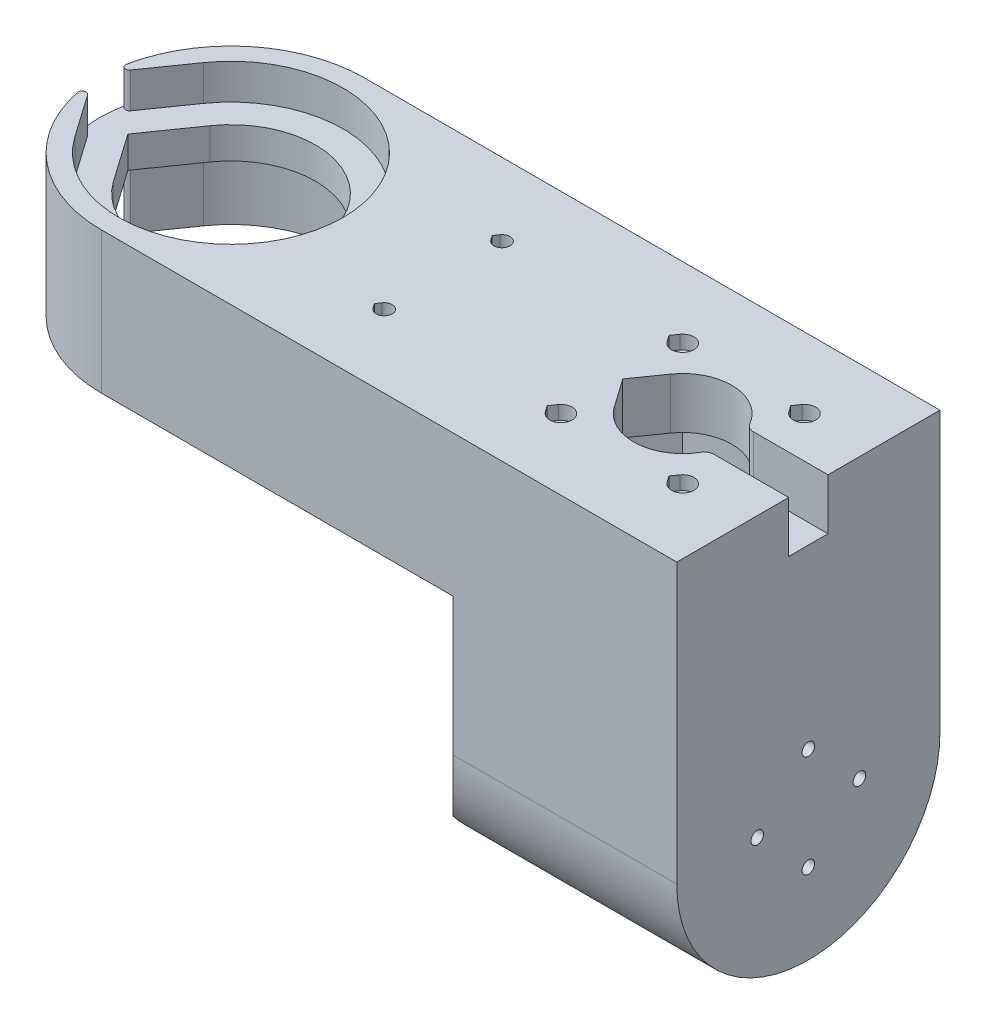
SolidWorks part; units mm, degrees
ref_plane "Front Plane" through (0, 0, 0) normal (1, 0, 0) x (0, 1, 0)
ref_plane "Top Plane" through (0, 0, 0) normal (0, 0, 1) x (0, 1, 0)
ref_plane "Right Plane" through (0, 0, 0) normal (0, 1, 0) x (-1, 0, 0)
sketch "Sketch1" plane through (0, 0, 0) normal (0, 0, 1) x (0, 1, 0)
  line L0 (45, 28.55) -> (54, 28.55)
  line L1 (-7, -93) -> (58, -93)
  line L2 (-7, -93) -> (-7, -137)
  line L3 (-7, -137) -> (58, -137)
  line L4 (58, -93) -> (58, -137)
  line L5 (59, 28.55) -> (68, 28.55)
  line L6 (59, 28.55) -> (59, -28.55)
  line L7 (59, -28.55) -> (68, -28.55)
  line L8 (68, 28.55) -> (68, -28.55)
  line L9 (45, 28.55) -> (45, -28.55)
  line L10 (45, -28.55) -> (54, -28.55)
  line L11 (54, 28.55) -> (54, -28.55)
  line L12 (-13, -147) -> (13, -147)
  line L13 (-30, 30.9464) -> (30, 30.9464) construction
  line L14 (-30, 30.9464) -> (-30, -30.2553) construction
  line L15 (-30, -30.2553) -> (30, -30.2553) construction
  line L16 (30, 30.9464) -> (30, -30.2553) construction
  line L17 (-25, -83) -> (81, -83)
  line L20 (81, -83) -> (81, -147)
  line L21 (81, -83) -> (35, -83)
  line L23 (81, 33.5) -> (35, 33.5)
  line L25 (-25, -147) -> (-13, -147)
  line L26 (-25, -147) -> (-25, -150)
  line L27 (-25, -150) -> (25, -150)
  line L28 (25, -147) -> (25, -150)
  line L29 (13, -147) -> (25, -147)
  line L30 (25, -147) -> (81, -147)
  line L31 (81, -83) -> (81, 33.5)
  line L32 (35, 33.5) -> (35, -83)
  line L33 (-25, -147) -> (-33.5, -147)
  line L34 (-25, -83) -> (-33.5, -83)
  line L35 (-33.5, -83) -> (-33.5, -147)
  point P8 (0, -30.2553)
  point P14 (68, 0)
  point P15 (58, -115)
  point P24 (45, 0)
  point P35 (0, -147)
  dimension "D1" = 65
  dimension "D2" = 44
  dimension "D3" = 57.1
  dimension "D4" = 9
  dimension "D5" = 57.1
  dimension "D6" = 9
  dimension "D7" = 115
  dimension "D8" = 60
  dimension "D9" = 5
  dimension "D10" = 15
  dimension "D11" = 10
  dimension "D12" = 3
  dimension "D13" = 50
  dimension "D14" = 26
  dimension "D15" = 10
  dimension "D16" = 23
  dimension "D17" = 4.95
  dimension "D18" = 10
  dimension "D19" = 10
  dimension "D20" = 8.5
extrude "Boss-Extrude1" add sketch "Sketch1" along normal blind 67 contours L29 L30 L20 L17 L25 L12 L1 L4 L3 L2 | L4 L1 L2 L3 | L23 L32 L17 L31 L0 L11 L10 L9 L5 L8 L7 L6 | L11 L0 L9 L10 | L8 L5 L6 L7 region at (0, 49.5, 0) region at (115, 25.5, 0) region at (0, 63.5, 0) region at (145.6883, -19, 0) region at (30.6232, 58.356, 0)
sketch "Sketch2" plane through (0, 81, 0) normal (0, 1, 0) x (-1, 0, 0)
  line L0 (-56.7259, 33.5) -> (49943.2741, 33.5) construction
  line L1 (-147, 67) -> (-147, 0) construction
  line L2 (17.6118, 21.1681) -> (26.2467, 33.5)
  line L3 (-115, -14.8158) -> (-54, -14.8158) construction
  line L4 (-93, 0) -> (-137, 0) construction
  line L5 (-93, 0) -> (-137, 0) construction
  line L9 (-147, 16) -> (-147, 51)
  line L10 (33.5473, 15.9815) -> (-147, 51) construction
  line L11 (33.5482, 51) -> (-147, 16) construction
  line L12 (-54, 18.5) -> (-54, 48.5) construction
  line L13 (-104.0826, 51) -> (-125.9174, 51)
  line L14 (-130.5, 49) -> (-99.5, 49) construction
  line L15 (-130.5, 49) -> (-130.5, 18) construction
  line L16 (-130.5, 18) -> (-99.5, 18) construction
  line L17 (-99.5, 49) -> (-99.5, 18) construction
  line L18 (-130.5, 49) -> (-99.5, 18) construction
  line L19 (-130.5, 18) -> (-99.5, 49) construction
  line L20 (-135.0826, 51) -> (-147, 51)
  line L21 (-135.0826, 16) -> (-147, 16)
  line L22 (-104.0826, 16) -> (-125.9174, 16)
  line L27 (33.5, 67) -> (-21.8575, 67)
  line L28 (33.5, 0) -> (33.5, 67)
  line L29 (33.5, 67) -> (-147, 67) construction
  line L30 (33.5, 0) -> (-21.8575, 0)
  line L31 (28.55, 0) -> (-28.55, 0) construction
  line L34 (23.3868, 17.1244) -> (34.8531, 33.5)
  line L35 (34.8531, 33.5) -> (23.3868, 49.8756)
  line L36 (26.2467, 33.5) -> (17.6118, 45.8319)
  line L37 (-94.9174, 16) -> (-66.0711, 16)
  line L38 (-94.9174, 51) -> (-66.0711, 51)
  line L39 (-61.0711, 11) -> (-61.0711, 0)
  line L40 (33.5, 0) -> (-147, 0) construction
  line L41 (-61.0711, 56) -> (-61.0711, 67)
  line L42 (33.5, 67) -> (-147, 67) construction
  line L43 (-61.0711, 0) -> (-21.8575, 0)
  line L44 (-61.0711, 67) -> (-21.8575, 67)
  arc A0 (23.3868, 49.8756) -> (23.3868, 17.1244) centre (0, 33.5) ccw
  arc A2 (-39.8663, 36.7683) -> (-39.8653, 30.2204) centre (0, 33.5) ccw
  arc A5 (-135.0826, 16) -> (-125.9174, 16) centre (-130.5, 18) ccw
  arc A6 (-104.0826, 16) -> (-94.9174, 16) centre (-99.5, 18) ccw
  arc A9 (-125.9174, 51) -> (-135.0826, 51) centre (-130.5, 49) ccw
  arc A11 (-94.9174, 51) -> (-104.0826, 51) centre (-99.5, 49) ccw
  arc A12 (17.6118, 45.8319) -> (17.6118, 21.1681) centre (0, 33.5) ccw
  arc A13 (17.6118, 45.8319) -> (17.6118, 21.1681) centre (0, 33.5) cw construction
  arc A15 (23.3868, 17.1244) -> (23.3868, 49.8756) centre (0, 33.5) ccw construction
  arc A16 (-66.0711, 16) -> (-61.0711, 11) centre (-66.0711, 11) cw
  arc A17 (-66.0711, 51) -> (-61.0711, 56) centre (-66.0711, 56) ccw
  point P4 (-56.7259, 33.5)
  point P9 (-56.75, 33.4953)
  point P23 (-115, 33.5)
  point P39 (33.5, 33.5)
  point P61 (-54, 33.5)
  dimension "D1" = 57.1
  dimension "D2" = 35
  dimension "D3" = 80
  dimension "D6" = 5
  dimension "D9" = 10
  dimension "D10" = 43
  dimension "D11" = 55
  dimension "D12" = 10
  dimension "D4" = 61
  dimension "D5" = 30
  dimension "D8" = 31
  dimension "D13" = 55
extrude "Cut-Extrude1" cut sketch "Sketch2" against normal through all both and the other way through all contours A12 L2 L36
fillet "Fillet3" radius 34 2 edges at (-33.5, 58, 0) (-33.5, 58, 67)
extrude "Cut-Extrude2" cut sketch "Sketch2<4>" against normal blind 10 and the other way through all contours L20 L9 L21 A5 L22 A6 L37 A16 L39 L43 L30 L28 L27 L44 L41 A17 L38 A11 L13 A9
sketch "Sketch2<4>" plane through (0, 81, 0) normal (0, 1, 0) x (-1, 0, 0) same geometry as "Sketch2"
extrude "Cut-Extrude3" cut sketch "Sketch2<5>" against normal blind 9 from surface contours A0 L34 L35 starting at face at (81.1646, 71, 33.5)
sketch "Sketch2<5>" plane through (0, 81, 0) normal (0, 1, 0) x (-1, 0, 0) same geometry as "Sketch2"
extrude "Cut-Extrude4" cut sketch "Sketch2<6>" along normal blind 19 from surface contours A0 L34 L35 starting at face at (-7.4528, 35, 33.5)
sketch "Sketch2<6>" plane through (0, 81, 0) normal (0, 1, 0) x (-1, 0, 0) same geometry as "Sketch2"
sketch "Sketch3" plane through (0, 71, 0) normal (0, 1, 0) x (-1, 0, 0)
  line L0 (-93, 0) -> (-137, 0) construction
  line L1 (-93, 0) -> (-137, 0)
  line L2 (-115, 33.5) -> (-50115, 33.5) construction
  line L4 (-99.7403, 33.5) -> (-104.3338, 40.0179)
  line L5 (-127.65, 49) -> (-127, 49) construction
  line L6 (-130.5, 49) -> (-99.5, 49) construction
  line L7 (-130.5, 49) -> (-130.5, 18) construction
  line L8 (-130.5, 18) -> (-99.5, 18) construction
  line L9 (-99.5, 49) -> (-99.5, 18) construction
  line L12 (-128.9, 49) -> (-128.5, 49) construction
  line L13 (-129.22, 49.96) -> (-128.5, 49)
  line L14 (-129.22, 48.04) -> (-128.5, 49)
  line L15 (-128.1793, 50.6543) -> (-127, 49)
  line L16 (-127, 49) -> (-128.1793, 47.3457)
  line L17 (-96, 49) -> (-97.1793, 47.3457)
  line L18 (-97.1793, 50.6543) -> (-96, 49)
  line L19 (-98.22, 48.04) -> (-97.5, 49)
  line L20 (-98.22, 49.96) -> (-97.5, 49)
  line L21 (-96, 18) -> (-97.1793, 16.3457)
  line L22 (-97.1793, 19.6543) -> (-96, 18)
  line L23 (-98.22, 17.04) -> (-97.5, 18)
  line L24 (-98.22, 18.96) -> (-97.5, 18)
  line L25 (-127, 18) -> (-128.1793, 16.3457)
  line L26 (-128.1793, 19.6543) -> (-127, 18)
  line L27 (-129.22, 17.04) -> (-128.5, 18)
  line L28 (-129.22, 18.96) -> (-128.5, 18)
  line L29 (-115, 0) -> (-115, 33.5) construction
  line L30 (-147, 38.5) -> (-126.4564, 38.5)
  line L32 (-147, 28.5) -> (-126.4564, 28.5)
  line L34 (-167.5436, 38.5) -> (-126.4564, 28.5) construction
  line L35 (-167.5436, 28.5) -> (-126.4564, 38.5) construction
  line L36 (-147, 38.5) -> (-147, 28.5)
  line L38 (-104.7606, 26.3303) -> (-99.7403, 33.5)
  arc A0 (-128.1793, 50.6543) -> (-128.1793, 47.3457) centre (-130.5, 49) ccw
  arc A1 (-129.22, 49.96) -> (-129.22, 48.04) centre (-130.5, 49) ccw
  arc A2 (-129.22, 49.96) -> (-129.22, 48.04) centre (-130.5, 49) cw construction
  arc A3 (-128.1793, 50.6543) -> (-133.0893, 47.8092) centre (-130.5, 49) cw construction
  arc A4 (-97.1793, 50.6543) -> (-97.1793, 47.3457) centre (-99.5, 49) ccw
  arc A5 (-98.22, 49.96) -> (-98.22, 48.04) centre (-99.5, 49) ccw
  arc A6 (-98.22, 49.96) -> (-98.22, 48.04) centre (-99.5, 49) cw construction
  arc A7 (-97.1793, 50.6543) -> (-102.0893, 47.8092) centre (-99.5, 49) cw construction
  arc A8 (-97.1793, 19.6543) -> (-97.1793, 16.3457) centre (-99.5, 18) ccw
  arc A9 (-98.22, 18.96) -> (-98.22, 17.04) centre (-99.5, 18) ccw
  arc A10 (-98.22, 18.96) -> (-98.22, 17.04) centre (-99.5, 18) cw construction
  arc A11 (-97.1793, 19.6543) -> (-102.0893, 16.8092) centre (-99.5, 18) cw construction
  arc A12 (-128.1793, 19.6543) -> (-128.1793, 16.3457) centre (-130.5, 18) ccw
  arc A13 (-129.22, 18.96) -> (-129.22, 17.04) centre (-130.5, 18) ccw
  arc A14 (-129.22, 18.96) -> (-129.22, 17.04) centre (-130.5, 18) cw construction
  arc A15 (-128.1793, 19.6543) -> (-133.0893, 16.8092) centre (-130.5, 18) cw construction
  arc A18 (-126.4564, 28.5) -> (-104.7606, 26.3303) centre (-115, 33.5) ccw
  arc A19 (-104.3338, 40.0179) -> (-126.4564, 38.5) centre (-115, 33.5) ccw
  arc A20 (-104.3338, 40.0179) -> (-104.7606, 26.3303) centre (-115, 33.5) cw construction
  point P8 (-115, 33.5)
  point P24 (-147, 33.5)
  point P63 (-115, 49)
  dimension "D2" = 5.7
  dimension "D3" = 3.2
  dimension "D8" = 25
  dimension "D1" = 31
  dimension "D4" = 0.65
  dimension "D5" = 0.4
  dimension "D9" = 10
  dimension "D6" = 2
  dimension "D7" = 2
extrude "Cut-Extrude5" cut sketch "Sketch3" against normal up to vertex (13 mm away) contours L32 A18 L38 L4 A19 L30 L36 | A13 L27 L28 | A9 L23 L24 | A5 L19 L20 | A1 L14 L13 up to point (137, 58, 0)
extrude "Cut-Extrude6" cut sketch "Sketch3<3>" against normal blind 3.5 contours A0 L16 L15 | A12 L25 L26 | A4 L17 L18 | A8 L21 L22
sketch "Sketch3<3>" plane through (0, 71, 0) normal (0, 1, 0) x (-1, 0, 0) same geometry as "Sketch3"
sketch "Sketch4" plane through (0, 71, 0) normal (0, 1, 0) x (-1, 0, 0)
  line L0 (-115, 33.5) -> (-54, 33.5) construction
  line L1 (-54, 48.5) -> (-54, 18.5) construction
  line L2 (-52.6894, 49.4177) -> (-52.0468, 48.5)
  line L3 (-52.6894, 47.5823) -> (-52.0468, 48.5)
  line L4 (-52.0468, 48.5) -> (-52.4, 48.5) construction
  line L7 (-52.6894, 19.4177) -> (-52.0468, 18.5)
  line L8 (-51.95, 48.5) -> (-51.4974, 48.5) construction
  line L9 (-51.4974, 48.5) -> (-52.3207, 47.3242)
  line L10 (-52.3207, 49.6758) -> (-51.4974, 48.5)
  line L11 (-52.6894, 17.5823) -> (-52.0468, 18.5)
  line L12 (-52.0468, 18.5) -> (-52.4, 18.5) construction
  line L13 (-52.9972, 18.5) -> (-51.4974, 18.5) construction
  line L14 (-51.4974, 18.5) -> (-52.3207, 17.3242)
  line L15 (-52.3207, 19.6758) -> (-51.4974, 18.5)
  arc A1 (-52.6894, 49.4177) -> (-52.6894, 47.5823) centre (-54, 48.5) ccw
  arc A2 (-52.6894, 49.4177) -> (-52.6894, 47.5823) centre (-54, 48.5) cw construction
  arc A4 (-52.6894, 19.4177) -> (-52.6894, 17.5823) centre (-54, 18.5) ccw
  arc A5 (-52.3207, 49.6758) -> (-52.3207, 47.3242) centre (-54, 48.5) ccw
  arc A6 (-52.3207, 49.6758) -> (-52.3207, 47.3242) centre (-54, 48.5) cw construction
  arc A7 (-52.6894, 19.4177) -> (-52.6894, 17.5823) centre (-54, 18.5) cw construction
  arc A8 (-52.3207, 19.6758) -> (-52.3207, 17.3242) centre (-54, 18.5) ccw
  arc A9 (-52.3207, 19.6758) -> (-52.3207, 17.3242) centre (-54, 18.5) cw construction
  point P5 (-54, 33.5)
  dimension "D3" = 3.2
  dimension "D5" = 3.2
  dimension "D7" = 4.1
  dimension "D6" = 4.1
  dimension "D1" = 61
  dimension "D2" = 30
  dimension "D4" = 55
  dimension "D8" = 55
  dimension "D9" = 55
  dimension "D10" = 55
extrude "Cut-Extrude7" cut sketch "Sketch4" against normal blind 10 contours A1 L3 L2 | A4 L11 L7
extrude "Cut-Extrude8" cut sketch "Sketch4<3>" against normal blind 7
sketch "Sketch4<3>" plane through (0, 71, 0) normal (0, 1, 0) x (-1, 0, 0) same geometry as "Sketch4"
sketch "Sketch6" plane through (0, 35, 0) normal (0, -1, 0) x (1, 0, 0)
  line L0 (0, 33.5) -> (-26.2467, 33.5) construction
  line L1 (0, 33.5) -> (25.8751, 21.4342) construction
  line L2 (25.8751, 21.4342) -> (39.4317, 21.4342) construction
  line L3 (39.4317, 21.4342) -> (39.4317, 46.3342) construction
  line L4 (39.4317, 46.3342) -> (39.4317, 51.5342) construction
  line L5 (39.4317, 21.4342) -> (39.4317, 16.3342) construction
  line L6 (39.4317, 16.3342) -> (39.4317, 11.1342) construction
  line L9 (69.4317, 33.5) -> (91.1, 33.5) construction
  line L10 (91.1, 36) -> (91.1, 31)
  line L13 (38.1211, 15.4165) -> (37.4785, 16.3342)
  line L14 (38.1211, 17.252) -> (37.4785, 16.3342)
  line L15 (37.4785, 16.3342) -> (37.8317, 16.3342) construction
  line L16 (37.3817, 16.3342) -> (36.9291, 16.3342) construction
  line L17 (36.9291, 16.3342) -> (37.7525, 17.5101)
  line L18 (37.7525, 15.1584) -> (36.9291, 16.3342)
  line L19 (38.1211, 45.4165) -> (37.4785, 46.3342)
  line L20 (38.1211, 47.252) -> (37.4785, 46.3342)
  line L21 (37.4785, 46.3342) -> (37.8317, 46.3342) construction
  line L22 (37.3817, 46.3342) -> (36.9291, 46.3342) construction
  line L23 (36.9291, 46.3342) -> (37.7525, 47.5101)
  line L24 (37.7525, 45.1584) -> (36.9291, 46.3342)
  line L25 (39.4317, 51.5342) -> (22.133, 51.5342)
  line L26 (39.4317, 11.1342) -> (17.7447, 11.1342)
  line L27 (39.4317, 11.1342) -> (54.4317, 11.1342)
  line L28 (39.4317, 51.5342) -> (54.4317, 51.5342)
  line L29 (54.4317, 51.5342) -> (54.4317, 43.5)
  line L30 (54.4317, 33.5) -> (69.4317, 33.5) construction
  line L31 (54.4317, 23.5) -> (54.4317, 11.1342)
  line L33 (54.4317, 23.5) -> (59.4317, 23.5)
  line L34 (54.4317, 43.5) -> (59.4317, 43.5)
  line L36 (59.4317, 23.5) -> (69.4317, 31)
  line L37 (59.4317, 43.5) -> (69.4317, 36)
  line L41 (69.4317, 36) -> (91.1, 36)
  line L42 (69.4317, 31) -> (91.1, 31)
  arc A0 (-23.3868, 17.1244) -> (-23.3868, 49.8756) centre (0, 33.5) ccw construction
  arc A5 (38.1211, 15.4165) -> (38.1211, 17.252) centre (39.4317, 16.3342) ccw
  arc A6 (38.1211, 15.4165) -> (38.1211, 17.252) centre (39.4317, 16.3342) cw construction
  arc A7 (37.7525, 15.1584) -> (37.7525, 17.5101) centre (39.4317, 16.3342) ccw
  arc A8 (37.7525, 15.1584) -> (37.7525, 17.5101) centre (39.4317, 16.3342) cw construction
  arc A9 (38.1211, 45.4165) -> (38.1211, 47.252) centre (39.4317, 46.3342) ccw
  arc A10 (38.1211, 45.4165) -> (38.1211, 47.252) centre (39.4317, 46.3342) cw construction
  arc A11 (37.7525, 45.1584) -> (37.7525, 47.5101) centre (39.4317, 46.3342) ccw
  arc A12 (37.7525, 45.1584) -> (37.7525, 47.5101) centre (39.4317, 46.3342) cw construction
  arc A13 (-23.3868, 17.1244) -> (-23.3868, 49.8756) centre (0, 33.5) ccw construction
  arc A14 (22.133, 51.5342) -> (17.7447, 11.1342) centre (0, 33.5) cw
  point P17 (72.1659, 33.5)
  dimension "D7" = 2.5
  dimension "D11" = 3.2
  dimension "D12" = 4.1
  dimension "D15" = 3.2
  dimension "D16" = 4.1
  dimension "D1" = 155
  dimension "D2" = 24.9
  dimension "D3" = 13.5566
  dimension "D4" = 5.2
  dimension "D5" = 5.2
  dimension "D6" = 5.1
  dimension "D13" = 55
  dimension "D14" = 55
  dimension "D17" = 55
  dimension "D18" = 55
  dimension "D19" = 15
  dimension "D20" = 20
  dimension "D21" = 15
  dimension "D22" = 5
  dimension "D23" = 5
sketch "Sketch10" plane through (0, -33.5, 0) normal (0, -1, 0) x (1, 0, 0)
  line L0 (83, 67) -> (147, 0) construction
  line L1 (83, 0) -> (147, 67) construction
  line L2 (83, 0) -> (147, 0) construction
  line L3 (93, 55.5) -> (137, 55.5)
  line L4 (93, 11.5) -> (137, 11.5)
  line L5 (137, 55.5) -> (137, 11.5)
  line L6 (93, 55.5) -> (137, 11.5) construction
  line L7 (93, 11.5) -> (137, 55.5) construction
  line L8 (93, 55.5) -> (93, 43.5)
  line L9 (137, 33.5) -> (83, 33.5) construction
  line L10 (83, 43.5) -> (83, 23.5)
  line L11 (83, 23.5) -> (93, 23.5)
  line L12 (83, 43.5) -> (93, 43.5)
  line L13 (93, 23.5) -> (93, 11.5)
  point P9 (115, 33.5)
  point P10 (115, 33.5)
  point P20 (83, 33.5)
  dimension "D1" = 44
  dimension "D2" = 20
extrude "Cut-Extrude18" cut sketch "Sketch10" against normal up to surface (91.5 mm away) up to face at (122.4062, 58, 33.4581)
extrude "Cut-Extrude11" cut sketch "Sketch6" against normal blind 10 contours L33 L36 L42 L10 L41 L37 L34 L29 L28 L25 A14 L26 L27 L31
extrude "Cut-Extrude12" cut sketch "Sketch6<4>" against normal blind 7 from surface contours A7 L17 L18 | A11 L23 L24 starting at face at (57.4813, 45, 32.7016)
sketch "Sketch6<4>" plane through (0, 35, 0) normal (0, -1, 0) x (1, 0, 0) same geometry as "Sketch6"
extrude "Cut-Extrude13" cut sketch "Sketch6<5>" against normal blind 3 from surface contours A5 L14 L13 | A9 L20 L19 starting at face at (38.7211, 52, 46.3342)
sketch "Sketch6<5>" plane through (0, 35, 0) normal (0, -1, 0) x (1, 0, 0) same geometry as "Sketch6"
fillet "Fillet5" radius 2.5 6 edges at (54.4317, 40, 43.5) (54.4317, 40, 23.5) (59.4317, 40, 43.5) (69.4317, 40, 36) (69.4317, 40, 31) (59.4317, 40, 23.5)
fillet "Fillet1" radius 5 2 edges at (61.0711, 76, 0) (61.0711, 76, 67)
fillet "Fillet2" radius 2.5 10 edges at (135.0826, 76, 16) (125.9174, 76, 16) (104.0826, 76, 16) (104.0826, 76, 51) (125.9174, 76, 51) (135.0826, 76, 51) (126.4564, 64.5, 28.5) (126.4564, 64.5, 38.5) (94.9174, 76, 51) (94.9174, 76, 16)
fillet "Fillet4" radius 1 4 edges at (-33.4026, 44.5, 31.4285) (-33.4026, 44.5, 35.5715) (-33.4026, 66.5, 35.5715) (-33.4026, 66.5, 31.4285)
chamfer "Chamfer7" distance 12 angle 45 2 edges at (93, 12.25, 43.5) (93, 12.25, 23.5)
chamfer "Chamfer5" distance 9.5 angle 45 2 edges at (83, 40, 36) (83, 40, 31)
sketch "Sketch11" plane through (137, 0, 0) normal (-1, 0, 0) x (0, -1, 0)
  line L0 (-71, 33.5) -> (-50071, 33.5) construction
  circle A0 centre (0, 33.5) radius 13 construction
  circle A1 centre (0, 33.5) radius 25
  circle A2 centre (0, 46.5) radius 1.6
  circle A3 centre (0, 46.5) radius 2.85
  circle A4 centre (13, 33.5) radius 2.85
  circle A5 centre (13, 33.5) radius 1.6
  circle A6 centre (0, 20.5) radius 2.85
  circle A7 centre (0, 20.5) radius 1.6
  circle A8 centre (-13, 33.5) radius 2.85
  circle A9 centre (-13, 33.5) radius 1.6
  dimension "D1" = 50
  dimension "D2" = 26
  dimension "D3" = 3.2
  dimension "D4" = 5.7
extrude "Cut-Extrude19" cut sketch "Sketch11" against normal through all contours A9 | A2 | A5 | A7
extrude "Cut-Extrude20" cut sketch "Sketch11<3>" against normal blind 3.5 contours A8 | A3 | A4 | A6
sketch "Sketch11<3>" plane through (137, 0, 0) normal (-1, 0, 0) x (0, -1, 0) same geometry as "Sketch11"
chamfer "Chamfer6" distance 7 angle 45 2 edges at (83, 0.75, 0) (83, 0.75, 67)
sketch "Sketch9" plane through (147, 0, 0) normal (1, 0, 0) x (0, 1, 0)
  line L0 (71, 33.5) -> (-49929, 33.5) construction
  line L2 (0, 67) -> (-54.5324, 67)
  line L4 (-54.5324, 67) -> (-54.5324, 0)
  line L5 (-54.5324, 0) -> (0, 0)
  arc A3 (0, 67) -> (0, 0) centre (0, 33.5) ccw
extrude "Cut-Extrude16" cut sketch "Sketch9" against normal up to surface (64 mm away) up to face at (83, 0.75, 52.75)
chamfer "Chamfer8" distance 5 angle 45 2 edges at (83, 1.8615, 45.5) (83, 1.8615, 21.5) first distance on face at (86.3773, 23.1701, 48.8773) first distance on face at (86.3773, 23.1701, 18.1227)
sketch "Sketch12" plane through (83, 0, 0) normal (-1, 0, 0) x (0, -1, 0)
  line L0 (25.2636, 55.5) -> (25.2636, 11.5)
  arc A0 (25.2636, 11.5) -> (25.2636, 55.5) centre (0, 33.5) ccw construction
  arc A1 (25.2636, 11.5) -> (25.2636, 55.5) centre (0, 33.5) ccw
extrude "Cut-Extrude21" cut sketch "Sketch12" against normal up to vertex (10 mm away) up to point (93, -25.2636, 11.5)
sketch "Sketch13" plane through (83, 0, 0) normal (-1, 0, 0) x (0, -1, 0)
  circle A0 centre (0, 46.5) radius 5
  circle A1 centre (0, 20.5) radius 5
  dimension "D1" = 10
  dimension "D2" = 10
extrude "Cut-Extrude22" cut sketch "Sketch13" against normal blind 10
fillet "Fillet6" radius 5 4 edges at (84.7678, -4.3094, 17.9645) (84.7678, 4.3094, 17.9645) (84.7678, -4.3094, 49.0355) (84.7678, 4.3094, 49.0355)
sketch "Sketch14" plane through (0, 81, 0) normal (0, 1, 0) x (-1, 0, 0)
  line L0 (-66.0711, 16) -> (-93.5, 16) construction
  line L1 (-105.5, 16) -> (-124.5, 16) construction
  line L2 (-136.5, 16) -> (-147, 16) construction
  line L3 (-147, 16) -> (-147, 0) construction
  line L4 (-147, 0) -> (-66.0711, 0) construction
  line L5 (-61.0711, 5) -> (-61.0711, 11) construction
  line L6 (-93.5, 51) -> (-66.0711, 51) construction
  line L7 (-61.0711, 56) -> (-61.0711, 62) construction
  line L8 (-66.0711, 67) -> (-147, 67) construction
  line L9 (-147, 67) -> (-147, 51) construction
  line L10 (-147, 51) -> (-136.5, 51) construction
  line L11 (-124.5, 51) -> (-105.5, 51) construction
  line L12 (-66.0711, 16) -> (-93.5, 16)
  line L13 (-105.5, 16) -> (-124.5, 16)
  line L14 (-136.5, 16) -> (-147, 16)
  line L15 (-147, 16) -> (-147, 0)
  line L16 (-147, 0) -> (-66.0711, 0)
  line L17 (-61.0711, 5) -> (-61.0711, 11)
  line L18 (-93.5, 51) -> (-66.0711, 51)
  line L19 (-61.0711, 56) -> (-61.0711, 62)
  line L20 (-66.0711, 67) -> (-147, 67)
  line L21 (-147, 67) -> (-147, 51)
  line L22 (-147, 51) -> (-136.5, 51)
  line L23 (-124.5, 51) -> (-105.5, 51)
  arc A0 (-93.5, 16) -> (-95.5, 15) centre (-93.5, 13.5) ccw construction
  arc A1 (-103.5, 15) -> (-95.5, 15) centre (-99.5, 18) ccw construction
  arc A2 (-103.5, 15) -> (-105.5, 16) centre (-105.5, 13.5) ccw construction
  arc A3 (-124.5, 16) -> (-126.5, 15) centre (-124.5, 13.5) ccw construction
  arc A4 (-134.5, 15) -> (-126.5, 15) centre (-130.5, 18) ccw construction
  arc A5 (-134.5, 15) -> (-136.5, 16) centre (-136.5, 13.5) ccw construction
  arc A6 (-66.0711, 0) -> (-61.0711, 5) centre (-66.0711, 5) ccw construction
  arc A7 (-61.0711, 11) -> (-66.0711, 16) centre (-66.0711, 11) ccw construction
  arc A8 (-95.5, 52) -> (-103.5, 52) centre (-99.5, 49) ccw construction
  arc A9 (-95.5, 52) -> (-93.5, 51) centre (-93.5, 53.5) ccw construction
  arc A10 (-66.0711, 51) -> (-61.0711, 56) centre (-66.0711, 56) ccw construction
  arc A11 (-61.0711, 62) -> (-66.0711, 67) centre (-66.0711, 62) ccw construction
  arc A12 (-136.5, 51) -> (-134.5, 52) centre (-136.5, 53.5) ccw construction
  arc A13 (-126.5, 52) -> (-134.5, 52) centre (-130.5, 49) ccw construction
  arc A14 (-126.5, 52) -> (-124.5, 51) centre (-124.5, 53.5) ccw construction
  arc A15 (-105.5, 51) -> (-103.5, 52) centre (-105.5, 53.5) ccw construction
  arc A16 (-93.5, 16) -> (-95.5, 15) centre (-93.5, 13.5) ccw
  arc A17 (-103.5, 15) -> (-95.5, 15) centre (-99.5, 18) ccw
  arc A18 (-103.5, 15) -> (-105.5, 16) centre (-105.5, 13.5) ccw
  arc A19 (-124.5, 16) -> (-126.5, 15) centre (-124.5, 13.5) ccw
  arc A20 (-134.5, 15) -> (-126.5, 15) centre (-130.5, 18) ccw
  arc A21 (-134.5, 15) -> (-136.5, 16) centre (-136.5, 13.5) ccw
  arc A22 (-66.0711, 0) -> (-61.0711, 5) centre (-66.0711, 5) ccw
  arc A23 (-61.0711, 11) -> (-66.0711, 16) centre (-66.0711, 11) ccw
  arc A24 (-95.5, 52) -> (-103.5, 52) centre (-99.5, 49) ccw
  arc A25 (-95.5, 52) -> (-93.5, 51) centre (-93.5, 53.5) ccw
  arc A26 (-66.0711, 51) -> (-61.0711, 56) centre (-66.0711, 56) ccw
  arc A27 (-61.0711, 62) -> (-66.0711, 67) centre (-66.0711, 62) ccw
  arc A28 (-136.5, 51) -> (-134.5, 52) centre (-136.5, 53.5) ccw
  arc A29 (-126.5, 52) -> (-134.5, 52) centre (-130.5, 49) ccw
  arc A30 (-126.5, 52) -> (-124.5, 51) centre (-124.5, 53.5) ccw
  arc A31 (-105.5, 51) -> (-103.5, 52) centre (-105.5, 53.5) ccw
extrude "Cut-Extrude23" cut sketch "Sketch14" against normal blind 10
